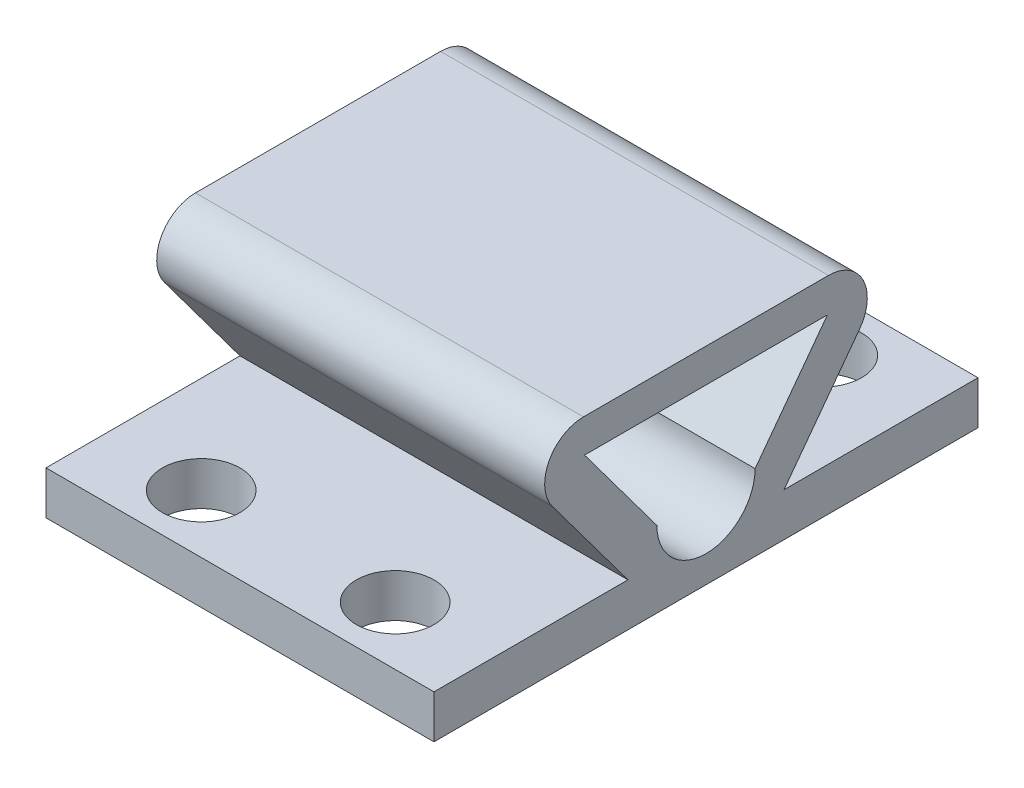
SolidWorks part; units mm, degrees
ref_plane "Front Plane" through (0, 0, 0) normal (0, 0, 1) x (1, 0, 0)
ref_plane "Top Plane" through (0, 0, 0) normal (0, 1, 0) x (1, 0, 0)
ref_plane "Right Plane" through (0, 0, 0) normal (1, 0, 0) x (0, 0, -1)
sketch "Sketch6" plane through (0, 0, 0) normal (1, 0, 0) x (0, 0, -1)
  line L0 (7.95, -9.7319) -> (3.2164, -16.0819)
  line L1 (-7.95, -9.7319) -> (-3.2164, -16.0819)
  line L2 (-7.95, -9.7319) -> (-3.81, -9.7319)
  line L3 (-13.0827, -7.5289) -> (-5.1089, -18.2252)
  line L4 (-5.1089, -18.2252) -> (-17.8089, -18.2252)
  line L5 (-17.8089, -18.2252) -> (-17.8089, -21.0616)
  line L6 (0, -16.0819) -> (0, 3.4101) construction
  line L7 (-17.8089, -21.0616) -> (17.8089, -21.0616)
  line L8 (-13.0827, -7.5289) -> (13.0827, -7.5289)
  line L9 (17.8089, -18.2252) -> (17.8089, -21.0616)
  line L10 (5.1089, -18.2252) -> (17.8089, -18.2252)
  line L11 (13.0827, -7.5289) -> (5.1089, -18.2252)
  line L12 (-3.81, -9.7319) -> (3.81, -9.7319)
  line L13 (7.95, -9.7319) -> (3.81, -9.7319)
  arc A1 (-3.2164, -16.0819) -> (3.2164, -16.0819) centre (0, -16.0819) ccw
  point P16 (0, -21.0616)
  dimension "D2" = 12.7
extrude "Boss-Extrude2" add sketch "Sketch6" along normal blind 25.4 contours L3 L4 L5 L7 L9 L10 L11 region at (0, -7.9099, 0)
sketch "Sketch12" plane through (0, -18.2252, 0) normal (0, 1, 0) x (1, 0, 0)
  line L0 (0, -5.1089) -> (0, -17.8089) construction
  line L1 (25.4, -17.8089) -> (0, -17.8089) construction
  circle A0 centre (6.35, -13.9989) radius 2.54
  dimension "D1" = 6.35
  dimension "D2" = 3.81
sketch "Sketch13" plane through (0, -18.2252, 0) normal (0, 1, 0) x (1, 0, 0)
  line L0 (25.4, -5.1089) -> (25.4, -17.8089) construction
  line L3 (25.4, -17.8089) -> (0, -17.8089) construction
  circle A0 centre (19.05, -13.9989) radius 2.54
  dimension "D1" = 6.35
  dimension "D2" = 3.81
extrude "Cut-Extrude4" cut sketch "Sketch13" against normal blind 6.35
extrude "Cut-Extrude5" cut sketch "Sketch12" against normal blind 6.35 contours A0
sketch "Sketch14" plane through (0, -18.2252, 0) normal (0, 1, 0) x (1, 0, 0)
  line L1 (25.4, 17.8089) -> (0, 17.8089) construction
  line L2 (25.4, 5.1089) -> (25.4, 17.8089) construction
  line L3 (0, 5.1089) -> (0, 17.8089) construction
  circle A0 centre (19.05, 13.9989) radius 2.54
  circle A1 centre (6.35, 13.9989) radius 2.54
  dimension "D1" = 3.81
  dimension "D2" = 3.81
  dimension "D3" = 6.35
  dimension "D4" = 6.35
extrude "Cut-Extrude6" cut sketch "Sketch14" against normal blind 6.35
extrude "Boss-Extrude3" add sketch "Sketch6<4>" along normal blind 2.54 contours A1 L0 L13 L12 L2 L1
sketch "Sketch6<4>" plane through (0, 0, 0) normal (1, 0, 0) x (0, 0, -1) same geometry as "Sketch6"
fillet "Fillet1" radius 2.54 1 edges at (12.7, -7.5289, 13.0827)
fillet "Fillet2" radius 2.54 1 edges at (12.7, -7.5289, -13.0827)
sketch "Sketch18" plane through (0, 0, 0) normal (-1, 0, 0) x (0, 0, 1)
  circle A0 centre (0, -16.0819) radius 3.175
extrude "Cut-Extrude7" cut sketch "Sketch18" against normal blind 2.54
